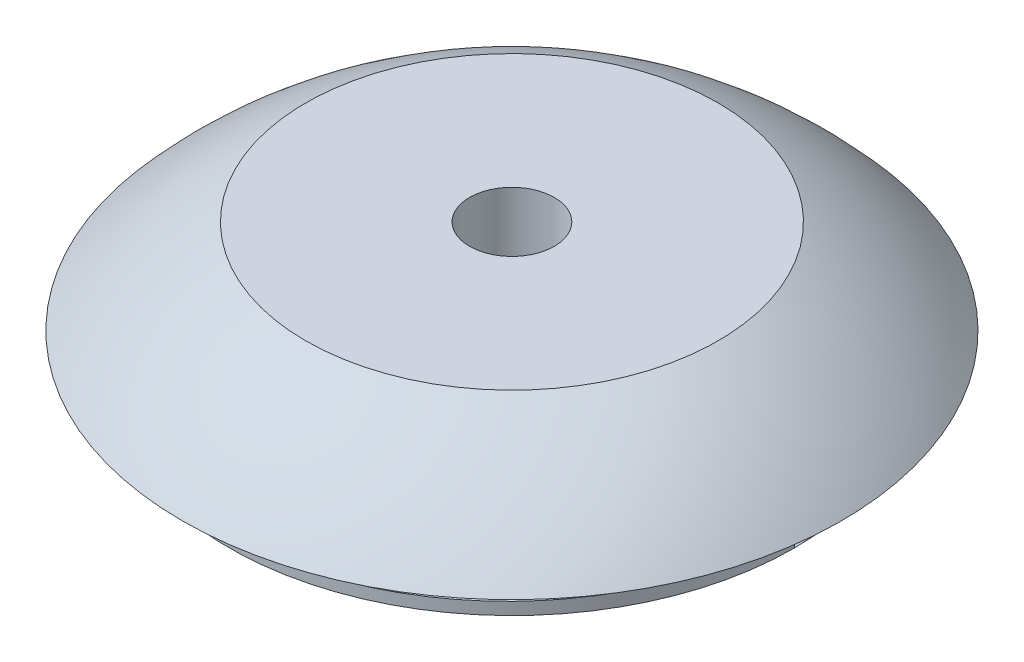
SolidWorks part; units mm, degrees
ref_plane "Front Plane" through (0, 0, 0) normal (0, 0, 1) x (1, 0, 0)
ref_plane "Top Plane" through (0, 0, 0) normal (0, 1, 0) x (1, 0, 0)
ref_plane "Right Plane" through (0, 0, 0) normal (1, 0, 0) x (0, 0, -1)
sketch "Sketch1" plane through (0, 0, 0) normal (0, 0, 1) x (1, 0, 0)
  line L0 (0, 76.9291) -> (0, -76.2616) construction
  line L1 (0, 0) -> (35, 0)
  line L2 (0, 14.1843) -> (0, 0)
  arc A1 (35, 0) -> (0, 14.1843) centre (3.2869, -27.979) ccw
revolve "Revolve1" add sketch "Sketch1" angle 360 about L0
sketch "Sketch2" plane through (0, 0, 0) normal (0, -1, 0) x (1, 0, 0)
  circle A0 centre (0, 0) radius 30
extrude "Boss-Extrude1" add sketch "Sketch2" along normal blind 5
thread "Thread1" pitch 1.5 method cut profile "Thread Profile1" start angle 0, offset 0, length 5, pitch 1.5, diameter 60
ref_plane "Plane1" through (30, -5, 0) normal (0, 0, 1) x (1, 0, 0)
sketch "Thread Profile1" plane through (30, -5, 0) normal (0, 0, 1) x (1, 0, 0)
  line L0 (0, 0) -> (0, 1.5) construction
  line L11 (0, 0) -> (0, 1.3125)
  line L12 (0, 1.3125) -> (-0.8119, 0.8437)
  line L13 (-0.8119, 0.8437) -> (-0.8119, 0.4687)
  line L15 (-0.8119, 0.4687) -> (0, 0)
  line L17 (-0.8119, 0.6562) -> (0, 0.6562) construction
  point P2 (0, 0)
  dimension "Pitch" = 1.5
  dimension "Profile_Angle" = 60
  dimension "Profile_Land" = 0.375
  dimension "Profile_Height" = 0.8119
ref_plane "Plane2" through (0, 10, 0) normal (0, 1, 0) x (1, 0, 0)
other "SurfaceCut2" flip cut yes
sketch "Sketch3" plane through (0, 10, 0) normal (0, 1, 0) x (1, 0, 0)
  circle A0 centre (0, 0) radius 4.5
extrude "Cut-Extrude1" cut sketch "Sketch3" against normal through all
